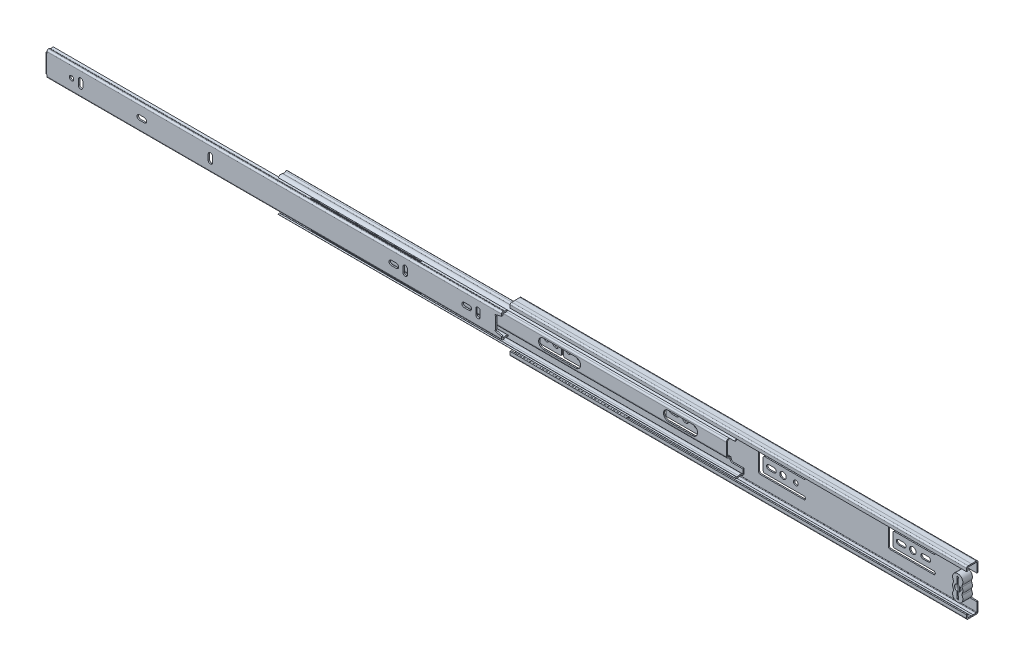
SolidWorks part; units mm, degrees
ref_plane "Front" through (0, 0, 0) normal (0, 0, 1) x (1, 0, 0)
ref_plane "Top" through (0, 0, 0) normal (0, 1, 0) x (1, 0, 0)
ref_plane "Right" through (0, 0, 0) normal (1, 0, 0) x (0, 0, -1)
sketch "Sketch1" plane through (0, 0, 0) normal (1, 0, 0) x (0, 0, -1)
  line L1 (5.6388, 0) -> (-5.6388, 0) construction
  line L4 (-4.1393, 22.8203) -> (-0.7433, 22.6989)
  line L5 (-1.1312, 21.5182) -> (-4.1819, 21.6273)
  line L6 (-4.445, 18.415) -> (-5.6388, 18.415)
  line L7 (-4.445, 21.3734) -> (-4.445, 18.415)
  line L8 (-5.6388, 18.415) -> (-5.6388, 21.3734)
  line L9 (3.9237, 21.6269) -> (0.7619, 21.5441)
  line L10 (5.6388, 0) -> (5.6388, 21.1191)
  line L11 (4.445, 21.1191) -> (4.445, 0)
  line L12 (5.6388, 0) -> (4.445, 0)
  line L13 (-0.7433, 22.6989) -> (3.8925, 22.8203)
  arc A0 (-4.445, 21.3734) -> (-4.1819, 21.6273) centre (-4.191, 21.3734) cw
  arc A1 (-5.6388, 21.3734) -> (-4.1393, 22.8203) centre (-4.191, 21.3734) cw
  arc A3 (3.9237, 21.6269) -> (4.445, 21.1191) centre (3.937, 21.1191) cw
  arc A4 (3.8925, 22.8203) -> (5.6388, 21.1191) centre (3.937, 21.1191) cw
  arc A5 (-1.1312, 21.5182) -> (0.7619, 21.5441) centre (-0.1524, 19.1744) cw
  dimension "D2" = 19.1744
  dimension "D7" = 0.254
  dimension "D8" = 0.508
  dimension "D6" = 2.54
  dimension "D9" = 1.1938
  dimension "D10" = 88.5
  dimension "D1" = 11.2776
  dimension "D3" = 5.7912
  dimension "D4" = 36.83
  dimension "D5" = 1.1938
  dimension "D11" = 87.953
  dimension "D12" = 45.6406
extrude "Extrude1" add sketch "Sketch1" along normal mid plane 450.088
ref_plane "Travel / 2" through (-453.644, 0, 0) normal (-1, 0, 0) x (0, 0, 1)
sketch "Sketch2" plane through (-453.644, 0, 0) normal (-1, 0, 0) x (0, 0, 1)
  line L0 (0.0254, 6.1159) -> (0.0254, 0)
  line L2 (-5.6388, 0) -> (5.6388, 0) construction
  line L3 (5.6388, 21.3734) -> (5.6388, 18.415) construction
  line L7 (-4.445, 21.1191) -> (-4.445, 0) construction
  line L8 (-5.6388, 0) -> (-5.6388, 21.1191) construction
  line L13 (-3.5306, 16.3766) -> (-3.5306, 9.5217)
  line L46 (-2.3867, 7.7262) -> (-0.4146, 6.8065)
  arc A0 (0.0254, 6.1159) -> (-0.4146, 6.8065) centre (-0.7366, 6.1159) ccw
  arc A1 (-1.5056, 17.2916) -> (1.2415, 16.9143) centre (0.1524, 19.1744) ccw
  arc A4 (1.1312, 21.5182) -> (-0.7619, 21.5441) centre (0.1524, 19.1744) ccw construction
  arc A19 (-3.5306, 9.5217) -> (-2.3867, 7.7262) centre (-1.5494, 9.5217) ccw
  arc A25 (-1.5056, 17.2916) -> (-3.5306, 16.3766) centre (-2.3114, 16.3766) ccw
  arc A51 (5.7404, 15.6277) -> (1.2415, 16.9143) centre (2.7686, 13.7451) ccw
  dimension "D2" = 8.4074
  dimension "D3" = 27.4903
  dimension "D6" = 1.9812
  dimension "D8" = 12.2319
  dimension "D10" = 2.5088
  dimension "D11" = 1.2192
  dimension "D4" = 0.762
  dimension "D5" = 4.4704
  dimension "D7" = 115
  dimension "D9" = 19.0435
  dimension "D13" = 11.3792
extrude "Middle Member" add sketch "Sketch2" against normal blind 450.088 separate body thin thin type one direction reverse wall 1.2192
ref_plane "Travel" through (-682.244, 0, 0) normal (-1, 0, 0) x (0, 0, 1)
sketch "Sketch3" plane through (-682.244, 0, 0) normal (-1, 0, 0) x (0, 0, 1)
  line L0 (1.2446, 0) -> (0.0254, 0) construction
  line L1 (-5.6388, 0) -> (-5.6388, 21.1191) construction
  line L56 (7.0612, 0) -> (7.0612, 10.6235)
  line L93 (5.5372, 12.1475) -> (5.1643, 12.1475)
  arc A0 (1.2082, 11.9072) -> (4.2365, 11.8325) centre (2.7686, 13.7451) ccw
  arc A29 (7.0612, 10.6235) -> (5.5372, 12.1475) centre (5.5372, 10.6235) ccw
  arc A53 (5.1643, 12.1475) -> (4.2365, 11.8325) centre (5.1643, 10.6235) ccw
  dimension "D1" = 1.524
  dimension "D4" = 1.524
  dimension "D5" = 2.411
  dimension "D2" = 12.7
  dimension "D3" = 12.1475
  dimension "D6" = 5.853
extrude "Drawer Member" add sketch "Sketch3" against normal blind 450.088 thin thin type one direction wall 1.397
sketch "Sketch6" plane through (0, 0, 7.0612) normal (0, 0, 1) x (1, 0, 0)
  line L1 (-682.244, 0) -> (-680.339, 0)
  line L2 (-682.244, 0) -> (-682.244, 12.1475)
  line L3 (-682.244, 12.1475) -> (-680.339, 12.1475)
  line L4 (-680.339, 0) -> (-680.339, 12.1475)
  line L5 (-232.156, 12.1475) -> (-682.244, 12.1475) construction
  line L7 (-682.244, 10.6235) -> (-682.244, 0) construction
  line L8 (-232.156, 0) -> (-682.244, 0) construction
  dimension "D1" = 1.905
extrude "Cut-Extrude1" cut sketch "Sketch6" against normal through all
sketch "Sketch7" plane through (0, 0, 0) normal (0, -1, 0) x (1, 0, 0)
  line L0 (-680.339, 7.0612) -> (-680.593, 7.0612)
  line L1 (-682.244, 5.4102) -> (-682.244, 0.3041)
  line L2 (-682.244, 0.3041) -> (-680.847, 0.3041)
  line L3 (-680.847, 0.3041) -> (-680.847, 5.4102)
  line L4 (-680.593, 5.6642) -> (-680.339, 5.6642)
  line L5 (-232.156, 5.6642) -> (-680.339, 5.6642) construction
  line L6 (-680.339, 7.0612) -> (-680.339, 5.6642)
  line L7 (-232.156, 0.3041) -> (-680.339, 0.3041) construction
  line L9 (-680.339, 5.087) -> (-680.339, 0.3041) construction
  arc A0 (-680.593, 5.6642) -> (-680.847, 5.4102) centre (-680.593, 5.4102) ccw
  arc A1 (-680.593, 7.0612) -> (-682.244, 5.4102) centre (-680.593, 5.4102) ccw
  dimension "D1" = 0.254
  dimension "D2" = 1.905
extrude "Extrude4" add sketch "Sketch7" against normal blind 8.89
sketch "Sketch8" plane through (0, 0, -4.445) normal (0, 0, 1) x (1, 0, 0)
  line L0 (215.4055, 7.6456) -> (216.8398, 7.493)
  line L1 (225.044, 12.2048) -> (215.6474, 12.2048)
  line L2 (216.8398, 7.493) -> (216.8398, 0)
  line L3 (225.044, 0) -> (-225.044, 0) construction
  line L4 (225.044, 21.1191) -> (225.044, 0) construction
  line L5 (225.044, 12.2048) -> (225.044, 0)
  line L6 (225.044, 0) -> (216.8398, 0)
  arc A0 (215.6474, 12.2048) -> (215.4055, 7.6456) centre (215.6474, 9.9188) ccw
  dimension "D3" = 9.9188
  dimension "D1" = 12.2048
  dimension "D2" = 8.2042
  dimension "D4" = 9.3966
  dimension "D5" = 7.493
extrude "Cut-Extrude2" cut sketch "Sketch8" against normal up to next (1.1938 mm away)
sketch "Sketch9" plane through (0, 0, -4.445) normal (0, 0, 1) x (1, 0, 0)
  line L0 (216.8398, 0) -> (-225.044, 0) construction
  line L1 (216.8398, 7.493) -> (215.4428, 7.493)
  line L2 (216.8398, 7.493) -> (216.8398, 0)
  line L3 (216.8398, 0) -> (215.4428, 0)
  line L4 (215.4428, 7.493) -> (215.4428, 0)
  dimension "D1" = 1.397
extrude "Extrude5" add sketch "Sketch9" along normal up to surface (8.89 mm away) up to face at (0, 19.8942, 4.445)
sketch "Sketch10" plane through (0, 0, 4.445) normal (0, 0, 1) x (1, 0, 0)
  line L0 (211.0613, 0) -> (212.9663, 0)
  line L1 (215.4269, 9.8425) -> (216.8557, 9.8425)
  line L2 (215.4269, 3.0936) -> (215.4269, 9.8425)
  line L3 (216.8557, 3.0936) -> (216.8557, 9.8425)
  line L6 (219.3163, 0) -> (221.2213, 0)
  line L7 (215.4428, 0) -> (-225.044, 0) construction
  line L8 (216.1413, 0) -> (216.1413, 4.4715) construction
  line L9 (215.4428, 0) -> (216.8398, 0) construction
  arc A0 (221.2213, 0) -> (220.4115, 2.7517) centre (216.1413, 0) ccw
  arc A1 (220.4115, 4.4715) -> (220.4115, 2.7517) centre (221.746, 3.6116) ccw
  arc A2 (220.4115, 4.4715) -> (211.8711, 4.4715) centre (216.1413, 7.2231) ccw
  arc A3 (211.8711, 2.7517) -> (211.8711, 4.4715) centre (210.5366, 3.6116) ccw
  arc A4 (211.8711, 2.7517) -> (211.0613, 0) centre (216.1413, 0) ccw
  arc A5 (215.4269, 3.0936) -> (212.9663, 0) centre (216.1413, 0) ccw
  arc A6 (219.3163, 0) -> (216.8557, 3.0936) centre (216.1413, 0) ccw
  dimension "D1" = 3.175
  dimension "D2" = 5.08
  dimension "D5" = 5.08
  dimension "D6" = 1.5875
  dimension "D3" = 9.8425
  dimension "D4" = 1.4288
  dimension "D7" = 7.2231
extrude "Extrude6" add sketch "Sketch10" along normal blind 1.016 and the other way offset from surface 0.508 separate body other way up to face at (119.624, 9.9327, -4.445)
sketch "Sketch11" plane through (0, 0, 7.0612) normal (0, 0, 1) x (1, 0, 0)
  line L0 (-237.871, 5.9678) -> (-237.871, 0)
  line L8 (-232.156, 8.5893) -> (-238.0153, 7.2212)
  line L11 (-237.871, 0) -> (-232.156, 0)
  line L12 (-232.156, 0) -> (-232.156, 8.5893)
  arc A1 (-238.0153, 7.2212) -> (-237.871, 5.9678) centre (-237.8709, 6.6028) ccw
  dimension "D3" = 0.635
  dimension "D1" = 5.715
  dimension "D2" = 8.5893
  dimension "D4" = 5.9678
  dimension "D5" = 103.143
extrude "Cut-Extrude3" cut sketch "Sketch11" against normal up to next (1.397 mm away)
sketch "Sketch12" plane through (0, 0, 1.2446) normal (0, 0, 1) x (1, 0, 0)
  line L0 (-3.556, 12.065) -> (-13.716, 12.065)
  line L1 (-3.556, 16.3766) -> (-3.556, 9.5217) construction
  line L2 (-16.256, 9.525) -> (-16.256, 0)
  line L3 (-3.556, 0) -> (-453.644, 0) construction
  line L4 (-16.256, 0) -> (-3.556, 0)
  line L5 (-3.556, 0) -> (-3.556, 12.065)
  arc A0 (-13.716, 12.065) -> (-16.256, 9.525) centre (-13.716, 9.525) ccw
  point P11 (-16.256, 12.065)
  dimension "D3" = 2.54
  dimension "D1" = 12.7
  dimension "D2" = 12.065
extrude "Cut-Extrude4" cut sketch "Sketch12" against normal through all
sketch "Sketch13" plane through (0, 0, -4.445) normal (0, 0, 1) x (1, 0, 0)
  line L0 (-156.6557, 7.112) -> (-181.4842, 7.112)
  line L1 (215.4428, 0) -> (-225.044, 0) construction
  line L2 (-164.7456, 0) -> (-164.7456, 4.2392) construction
  line L3 (-207.5827, 10.287) -> (-156.6557, 10.287)
  line L4 (-225.044, 21.1191) -> (-225.044, 0) construction
  line L5 (-185.2942, 7.112) -> (-207.5827, 7.112)
  line L6 (-184.5322, 0) -> (-184.5322, 6.35)
  line L7 (-182.2462, 6.35) -> (-182.2462, 0)
  line L8 (-162.2691, 2.286) -> (-167.2221, 2.286)
  line L13 (-201.3216, 0) -> (-196.7496, 0)
  line L14 (-193.219, 0) -> (-186.869, 0)
  line L15 (-184.5322, 0) -> (-182.2462, 0)
  line L16 (-179.7316, 0) -> (-175.1596, 0)
  line L17 (-169.5081, 0) -> (-159.9831, 0)
  arc A1 (-207.5827, 10.287) -> (-207.5827, 7.112) centre (-207.5827, 8.6995) ccw
  arc A2 (-184.5322, 6.35) -> (-185.2942, 7.112) centre (-185.2942, 6.35) ccw
  arc A4 (-181.4842, 7.112) -> (-182.2462, 6.35) centre (-181.4842, 6.35) ccw
  arc A7 (-156.6557, 7.112) -> (-156.6557, 10.287) centre (-156.6557, 8.6995) ccw
  arc A8 (-186.869, 0) -> (-193.219, 0) centre (-190.044, 0) ccw
  arc A9 (-196.7496, 0) -> (-201.3216, 0) centre (-199.0356, 0) ccw
  arc A10 (-175.1596, 0) -> (-179.7316, 0) centre (-177.4456, 0) ccw
  arc A11 (-159.9831, 0) -> (-162.2691, 2.286) centre (-162.2691, 0) ccw
  arc A12 (-167.2221, 2.286) -> (-169.5081, 0) centre (-167.2221, 0) ccw
  dimension "D3" = 2.286
  dimension "D4" = 3.175
  dimension "D7" = 8.9916
  dimension "D8" = 21.59
  dimension "D9" = 34.29
  dimension "D10" = 0.762
  dimension "D11" = 17.5387
  dimension "D12" = 9.525
  dimension "D13" = 5.5118
  dimension "D14" = 35
  dimension "D1" = 3.175
  dimension "D2" = 50.927
  dimension "D5" = 2.286
  dimension "D6" = 10.287
extrude "Cut-Extrude5" cut sketch "Sketch13" against normal up to next (1.1938 mm away)
sketch "Sketch32" plane through (0, 0, -5.6388) normal (0, 0, -1) x (-1, 0, 0)
  line L0 (44.5815, 0) -> (54.1065, 0)
  line L1 (58.869, 0) -> (65.219, 0)
  line L2 (68.7115, 0) -> (78.2365, 0)
  line L3 (81.602, 0) -> (86.174, 0)
  line L4 (-216.8398, 0) -> (159.9831, 0) construction
  line L5 (207.5827, 10.287) -> (156.6557, 10.287) construction
  line L6 (156.6557, 7.112) -> (181.4842, 7.112) construction
  line L7 (73.474, 2.286) -> (73.474, -3.4269) construction
  line L8 (49.344, 2.286) -> (49.344, -3.4269) construction
  line L14 (41.4065, 10.287) -> (84.65, 10.287)
  line L15 (80.078, 7.112) -> (41.4065, 7.112)
  line L17 (86.174, 8.763) -> (86.174, 0)
  line L18 (81.602, 0) -> (81.602, 5.588)
  line L23 (46.8675, 2.286) -> (51.8205, 2.286)
  line L25 (70.9975, 2.286) -> (75.9505, 2.286)
  arc A0 (193.219, 0) -> (186.869, 0) centre (190.044, 0) ccw construction
  arc A13 (86.174, 8.763) -> (84.65, 10.287) centre (84.65, 8.763) ccw
  arc A14 (81.602, 5.588) -> (80.078, 7.112) centre (80.078, 5.588) ccw
  arc A17 (41.4065, 10.287) -> (41.4065, 7.112) centre (41.4065, 8.6995) ccw
  arc A20 (54.1065, 0) -> (51.8205, 2.286) centre (51.8205, 0) ccw
  arc A21 (46.8675, 2.286) -> (44.5815, 0) centre (46.8675, 0) ccw
  arc A22 (65.219, 0) -> (58.869, 0) centre (62.044, 0) ccw
  arc A24 (78.2365, 0) -> (75.9505, 2.286) centre (75.9505, 0) ccw
  arc A25 (70.9975, 2.286) -> (68.7115, 0) centre (70.9975, 0) ccw
  dimension "D2" = 1.524
  dimension "D3" = 3.175
  dimension "D4" = 9.525
  dimension "D5" = 2.286
  dimension "D6" = 11.43
  dimension "D7" = 12.7
  dimension "D8" = 24.13
  dimension "D9" = 20.6375
  dimension "D10" = 128
  dimension "D1" = 4.572
extrude "Cut-Extrude14" cut sketch "Sketch32" against normal up to next (1.1938 mm away)
sketch "Sketch33" plane through (83.6094, 0.8125, -5.6388) normal (0, 0, -1) x (-1, 0, 0)
  line L0 (32.1909, -0.8125) -> (41.7159, -0.8125) construction
  line L1 (46.4784, -0.8125) -> (52.8284, -0.8125)
  line L2 (56.3209, -0.8125) -> (65.8459, -0.8125)
  line L3 (69.2114, -0.8125) -> (73.7834, -0.8125)
  line L4 (34.6674, -0.8125) -> (39.2394, -0.8125)
  line L7 (61.0834, 1.4735) -> (61.0834, -4.2394) construction
  line L8 (36.9534, 1.4735) -> (36.9534, -3.4269) construction
  line L9 (-133.2304, -0.8125) -> (128.1909, -0.8125) construction
  line L10 (168.2594, 9.4745) -> (125.0159, 9.4745) construction
  line L11 (125.0159, 6.2995) -> (163.6874, 6.2995) construction
  line L14 (29.0159, 9.4745) -> (72.2594, 9.4745)
  line L15 (67.6874, 6.2995) -> (29.0159, 6.2995)
  line L17 (73.7834, 7.9505) -> (73.7834, -0.8125)
  line L18 (69.2114, -0.8125) -> (69.2114, 4.7755)
  line L23 (34.4769, 1.4735) -> (39.4299, 1.4735) construction
  line L25 (58.6069, 1.4735) -> (63.5599, 1.4735)
  arc A0 (39.2394, -0.8125) -> (34.6674, -0.8125) centre (36.9534, -0.8125) ccw
  arc A1 (276.8284, -0.8125) -> (270.4784, -0.8125) centre (273.6534, -0.8125) ccw construction
  arc A13 (73.7834, 7.9505) -> (72.2594, 9.4745) centre (72.2594, 7.9505) ccw
  arc A14 (69.2114, 4.7755) -> (67.6874, 6.2995) centre (67.6874, 4.7755) ccw
  arc A17 (29.0159, 9.4745) -> (29.0159, 6.2995) centre (29.0159, 7.887) ccw
  arc A20 (41.7159, -0.8125) -> (39.4299, 1.4735) centre (39.4299, -0.8125) ccw construction
  arc A21 (34.4769, 1.4735) -> (32.1909, -0.8125) centre (34.4769, -0.8125) ccw construction
  arc A22 (52.8284, -0.8125) -> (46.4784, -0.8125) centre (49.6534, -0.8125) ccw
  arc A24 (65.8459, -0.8125) -> (63.5599, 1.4735) centre (63.5599, -0.8125) ccw
  arc A25 (58.6069, 1.4735) -> (56.3209, -0.8125) centre (58.6069, -0.8125) ccw
  dimension "D2" = 1.524
  dimension "D3" = 3.175
  dimension "D4" = 9.525
  dimension "D5" = 2.286
  dimension "D6" = 11.43
  dimension "D7" = 12.7
  dimension "D8" = 24.13
  dimension "D9" = 20.6375
  dimension "D10" = 224
  dimension "D1" = 4.572
extrude "Cut F" cut sketch "Sketch33" against normal up to next (1.1938 mm away)
sketch "Sketch34" plane through (169.8236, 1.4527, -5.6388) normal (0, 0, -1) x (-1, 0, 0)
  line L0 (-9.5949, -1.4527) -> (-0.0699, -1.4527)
  line L1 (4.6926, -1.4527) -> (11.0426, -1.4527)
  line L2 (14.5351, -1.4527) -> (24.0601, -1.4527)
  line L3 (27.4256, -1.4527) -> (31.9976, -1.4527)
  line L4 (-47.0162, -1.4527) -> (120.8816, -1.4527) construction
  line L7 (19.2976, 0.8333) -> (19.2976, -4.8796) construction
  line L8 (-4.8324, 0.8333) -> (-4.8324, -4.0671) construction
  line L9 (254.4736, 8.8343) -> (211.2301, 8.8343) construction
  line L10 (211.2301, 5.6593) -> (249.9016, 5.6593) construction
  line L14 (-12.7699, 8.8343) -> (30.4736, 8.8343)
  line L15 (25.9016, 5.6593) -> (-12.7699, 5.6593)
  line L17 (31.9976, 7.3103) -> (31.9976, -1.4527)
  line L18 (27.4256, -1.4527) -> (27.4256, 4.1353)
  line L23 (-7.3089, 0.8333) -> (-2.3559, 0.8333)
  line L25 (16.8211, 0.8333) -> (21.7741, 0.8333)
  arc A0 (363.0426, -1.4527) -> (356.6926, -1.4527) centre (359.8676, -1.4527) ccw construction
  arc A13 (31.9976, 7.3103) -> (30.4736, 8.8343) centre (30.4736, 7.3103) ccw
  arc A14 (27.4256, 4.1353) -> (25.9016, 5.6593) centre (25.9016, 4.1353) ccw
  arc A17 (-12.7699, 8.8343) -> (-12.7699, 5.6593) centre (-12.7699, 7.2468) ccw
  arc A20 (-0.0699, -1.4527) -> (-2.3559, 0.8333) centre (-2.3559, -1.4527) ccw
  arc A21 (-7.3089, 0.8333) -> (-9.5949, -1.4527) centre (-7.3089, -1.4527) ccw
  arc A22 (11.0426, -1.4527) -> (4.6926, -1.4527) centre (7.8676, -1.4527) ccw
  arc A24 (24.0601, -1.4527) -> (21.7741, 0.8333) centre (21.7741, -1.4527) ccw
  arc A25 (16.8211, 0.8333) -> (14.5351, -1.4527) centre (16.8211, -1.4527) ccw
  dimension "D2" = 1.524
  dimension "D3" = 3.175
  dimension "D4" = 9.525
  dimension "D5" = 2.286
  dimension "D6" = 11.43
  dimension "D7" = 12.7
  dimension "D8" = 24.13
  dimension "D9" = 20.6375
  dimension "D10" = 352
  dimension "D1" = 4.572
extrude "Cut G" cut sketch "Sketch34" against normal up to next (1.1938 mm away)
sketch "Sketch31" plane through (0, 0, -5.6388) normal (0, 0, -1) x (-1, 0, 0)
  line L0 (-225.044, 12.2048) -> (-225.044, 21.1191) construction
  line L1 (-216.8398, 0) -> (-179.4185, 0) construction
  line L2 (-209.169, 0) -> (-202.819, 0)
  arc A0 (-202.819, 0) -> (-209.169, 0) centre (-205.994, 0) ccw
  dimension "D1" = 19.05
  dimension "D2" = 6.35
extrude "Cut-Extrude15" cut sketch "Sketch31" against normal up to next (1.1938 mm away)
sketch "Sketch24" plane through (0, 0, 7.0612) normal (0, 0, 1) x (1, 0, 0)
  line L0 (-237.871, 0) -> (-680.593, 0) construction
  line L1 (-647.192, 4.826) -> (-647.192, 0) construction
  line L2 (-649.3764, 2.6416) -> (-649.3764, 0)
  line L3 (-649.3764, 0) -> (-645.0076, 0)
  line L4 (-645.0076, 0) -> (-645.0076, 2.6416)
  line L5 (-591.5025, 0) -> (-581.9775, 0)
  line L6 (-589.2165, 2.286) -> (-584.2635, 2.286)
  line L8 (-521.3764, 2.6416) -> (-521.3764, 0)
  line L9 (-521.3764, 0) -> (-517.0076, 0)
  line L10 (-517.0076, 0) -> (-517.0076, 2.6416)
  line L11 (-682.244, 8.89) -> (-682.244, 0) construction
  line L12 (-586.74, 2.286) -> (-586.74, 0) construction
  circle A0 centre (-656.082, 0) radius 2.1844
  arc A1 (-649.3764, 2.6416) -> (-645.0076, 2.6416) centre (-647.192, 2.6416) cw
  arc A2 (-591.5025, 0) -> (-589.2165, 2.286) centre (-589.2165, 0) cw
  arc A3 (-584.2635, 2.286) -> (-581.9775, 0) centre (-584.2635, 0) cw
  arc A4 (-521.3764, 2.6416) -> (-517.0076, 2.6416) centre (-519.192, 2.6416) cw
  dimension "D1" = 4.3688
  dimension "D4" = 8.89
  dimension "D5" = 2.286
  dimension "D7" = 60.452
  dimension "D8" = 128
  dimension "D2" = 35.052
  dimension "D3" = 4.826
  dimension "D6" = 9.525
extrude "Cut-Extrude13" cut sketch "Sketch24" against normal up to next (1.397 mm away)
sketch "Sketch25" plane through (0, 0, 7.0612) normal (0, 0, 1) x (1, 0, 0)
  line L0 (-257.4544, 0) -> (-253.0856, 0)
  line L1 (-237.871, 0) -> (-517.0076, 0) construction
  line L2 (-253.0856, 0) -> (-253.0856, 2.6416)
  line L3 (-257.4544, 2.6416) -> (-257.4544, 0)
  line L4 (-517.0076, 0) -> (-517.0076, 2.6416) construction
  line L5 (-261.6835, 0) -> (-271.2085, 0)
  line L6 (-584.2635, 2.286) -> (-589.2165, 2.286) construction
  line L7 (-268.9225, 2.286) -> (-263.9695, 2.286)
  line L8 (-266.446, 0) -> (-266.446, 2.286) construction
  arc A0 (-253.0856, 2.6416) -> (-257.4544, 2.6416) centre (-255.27, 2.6416) ccw
  arc A1 (-517.0076, 2.6416) -> (-521.3764, 2.6416) centre (-519.192, 2.6416) ccw construction
  arc A2 (-645.0076, 2.6416) -> (-649.3764, 2.6416) centre (-647.192, 2.6416) ccw construction
  arc A3 (-268.9225, 2.286) -> (-271.2085, 0) centre (-268.9225, 0) ccw
  arc A4 (-263.9695, 2.286) -> (-261.6835, 0) centre (-263.9695, 0) cw
  arc A5 (-581.9775, 0) -> (-584.2635, 2.286) centre (-584.2635, 0) ccw construction
  dimension "D1" = 391.922
  dimension "D2" = 11.176
extrude "Cut E" cut sketch "Sketch25" against normal up to next (1.397 mm away)
sketch "Sketch35" plane through (0, 0, 7.0612) normal (0, 0, 1) x (1, 0, 0)
  line L0 (-329.3364, 0) -> (-324.9676, 0)
  line L1 (-324.9676, 0) -> (-324.9676, 2.6416)
  line L2 (-329.3364, 2.6416) -> (-329.3364, 0)
  line L3 (-333.5655, 0) -> (-343.0905, 0)
  line L4 (-340.8045, 2.286) -> (-335.8515, 2.286)
  line L5 (-338.328, 2.286) -> (-338.328, -4.2491) construction
  line L6 (-253.0856, 0) -> (-253.0856, 2.6416) construction
  line L10 (-271.2085, 0) -> (-517.0076, 0) construction
  line L11 (-263.9695, 2.286) -> (-268.9225, 2.286) construction
  arc A0 (-324.9676, 2.6416) -> (-329.3364, 2.6416) centre (-327.152, 2.6416) ccw
  arc A1 (-340.8045, 2.286) -> (-343.0905, 0) centre (-340.8045, 0) ccw
  arc A2 (-335.8515, 2.286) -> (-333.5655, 0) centre (-335.8515, 0) cw
  arc A3 (-253.0856, 2.6416) -> (-257.4544, 2.6416) centre (-255.27, 2.6416) ccw construction
  arc A5 (-645.0076, 2.6416) -> (-649.3764, 2.6416) centre (-647.192, 2.6416) ccw construction
  dimension "D2" = 320.04
  dimension "D1" = 11.176
extrude "Cut C" cut sketch "Sketch35" against normal up to next (1.397 mm away)
sketch "Sketch26" plane through (0, 0, 1.2446) normal (0, 0, 1) x (1, 0, 0)
  line L0 (-201.3216, 0) -> (-159.9831, 0)
  line L1 (-196.4956, 4.826) -> (-164.8091, 4.826)
  line L2 (-44.5815, 0) -> (-78.2365, 0)
  line L3 (-73.4105, 4.826) -> (-49.4075, 4.826)
  line L4 (51.4185, 0) -> (17.7635, 0)
  line L5 (22.5895, 4.826) -> (46.5925, 4.826)
  arc A0 (-201.3216, 0) -> (-196.4956, 4.826) centre (-196.4956, 0) cw
  arc A1 (-159.9831, 0) -> (-164.8091, 4.826) centre (-164.8091, 0) ccw
  arc A2 (-78.2365, 0) -> (-73.4105, 4.826) centre (-73.4105, 0) cw
  arc A3 (-49.4075, 4.826) -> (-44.5815, 0) centre (-49.4075, 0) cw
  arc A4 (-44.5815, 0) -> (-46.8675, 2.286) centre (-46.8675, 0) ccw construction
  arc A5 (-75.9505, 2.286) -> (-78.2365, 0) centre (-75.9505, 0) ccw construction
  arc A6 (17.7635, 0) -> (22.5895, 4.826) centre (22.5895, 0) cw
  arc A7 (46.5925, 4.826) -> (51.4185, 0) centre (46.5925, 0) cw
  dimension "D1" = 4.826
extrude "Cut-Extrude17" cut sketch "Sketch26" against normal up to next (1.2192 mm away)
ref_plane "Plane3" through (-212.344, 0, 0) normal (-1, 0, 0) x (0, 0, 1)
sketch "Sketch27" plane through (-212.344, 0, 0) normal (-1, 0, 0) x (0, 0, 1)
  line L0 (0.1524, 21.6832) -> (0.1524, 16.6656)
  line L1 (0.1524, 23.635) -> (0.1524, 15.2838) construction
  arc A0 (0.1524, 16.6656) -> (0.1524, 21.6832) centre (0.1524, 19.1744) ccw
  arc A1 (-1.5056, 17.2916) -> (1.2415, 16.9143) centre (0.1524, 19.1744) ccw construction
revolve "Revolve1" add sketch "Sketch27" angle 360 about L1
pattern_linear "LPattern1" count 6 spacing 19.05 along (1, 0, 0) of bodies 128
sketch "Sketch28" plane through (-212.344, 0, 0) normal (-1, 0, 0) x (0, 0, 1)
  line L0 (2.6612, 19.1744) -> (-2.3564, 19.1744) construction
  line L1 (3.9624, 18.7934) -> (-3.6576, 18.7934)
  line L2 (3.9624, 18.7934) -> (3.9624, 19.5554)
  line L3 (3.9624, 19.5554) -> (-3.6576, 19.5554)
  line L4 (-3.6576, 18.7934) -> (-3.6576, 19.5554)
  line L5 (0.1524, 20.5465) -> (0.1524, 17.804) construction
  circle A1 centre (0.1524, 19.1744) radius 2.5088 construction
  point P8 (0.1524, 19.1744)
  dimension "D1" = 7.62
  dimension "D2" = 0.762
extrude "Extrude7" add sketch "Sketch28" along normal blind 6.35 and the other way blind 101.6
ref_plane "Plane4" through (-415.544, 0, 0) normal (-1, 0, 0) x (0, 0, 1)
sketch "Sketch29" plane through (-415.544, 0, 0) normal (-1, 0, 0) x (0, 0, 1)
  line L0 (2.7686, 16.0438) -> (2.7686, 11.4464)
  line L1 (2.7686, 16.6801) -> (2.7686, 10.2973) construction
  arc A0 (2.7686, 11.4464) -> (2.7686, 16.0438) centre (2.7686, 13.7451) ccw
  arc A1 (4.7105, 14.9753) -> (1.7707, 15.816) centre (2.7686, 13.7451) ccw construction
revolve "Revolve2" add sketch "Sketch29" angle 360 about L1
pattern_linear "LPattern2" count 6 spacing 19.05 along (1, 0, 0) of bodies 135
sketch "Sketch30" plane through (-415.544, 0, 0) normal (-1, 0, 0) x (0, 0, 1)
  line L0 (0.4699, 13.7451) -> (5.0673, 13.7451) construction
  line L1 (3.9624, 18.7934) -> (3.9624, 19.5554) construction
  line L2 (0.2286, 14.1261) -> (5.3086, 14.1261)
  line L3 (0.2286, 14.1261) -> (0.2286, 13.3641)
  line L4 (0.2286, 13.3641) -> (5.3086, 13.3641)
  line L5 (5.3086, 14.1261) -> (5.3086, 13.3641)
  line L7 (2.7686, 14.2437) -> (2.7686, 12.7853) construction
  circle A0 centre (2.7686, 13.7451) radius 2.2987 construction
  point P4 (2.7686, 13.7451)
  dimension "D1" = 5.08
extrude "Extrude8" add sketch "Sketch30" along normal blind 6.35 and the other way blind 101.6
mirror "Mirror3" about plane through (0, 0, 0) normal (0, 1, 0) of bodies 117 165 163 159 124 126 127 119
mirror "Mirror5" about plane through (0, 0, 0) normal (0, 1, 0) of bodies 141 134
